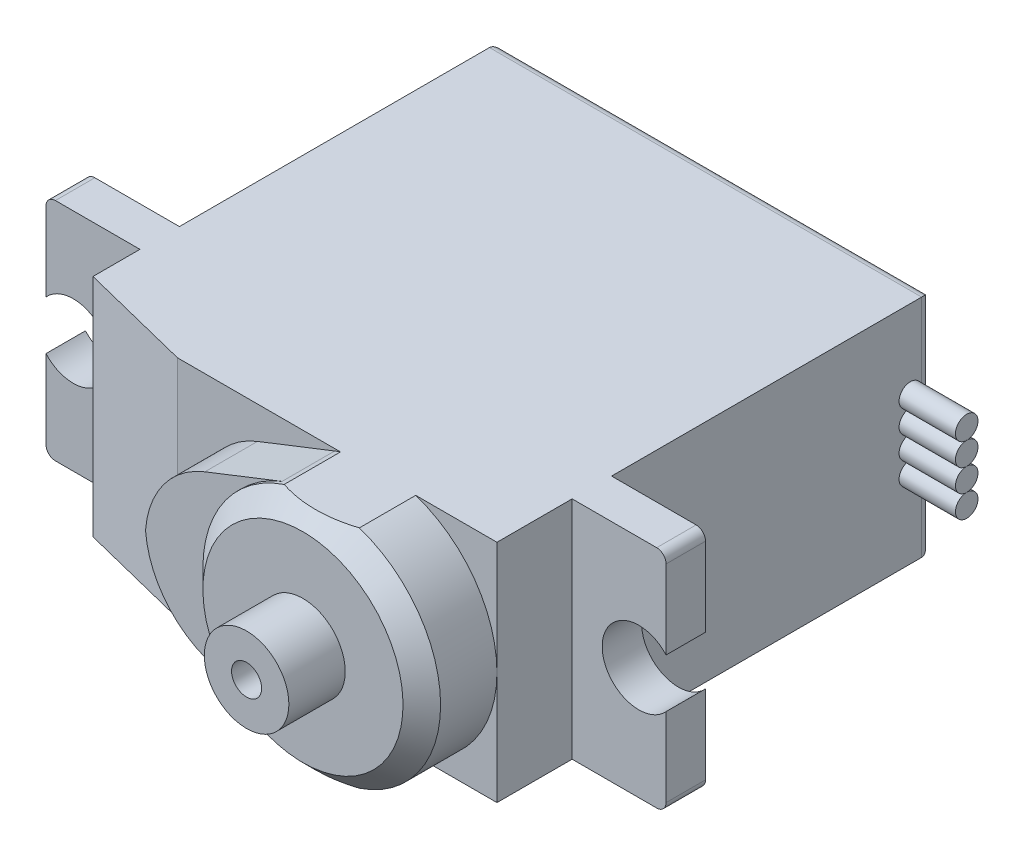
SolidWorks part; units mm, degrees
ref_plane "Plan de face" through (0, 0, 0) normal (0, 0, 1) x (1, 0, 0)
ref_plane "Plan de dessus" through (0, 0, 0) normal (0, 1, 0) x (1, 0, 0)
ref_plane "Plan de droite" through (0, 0, 0) normal (1, 0, 0) x (0, 0, -1)
sketch "Esquisse1" plane through (0, 0, 0) normal (0, 0, 1) x (1, 0, 0)
  line L1 (-11.5, -6) -> (11.5, -6)
  line L2 (-11.5, -6) -> (-11.5, 6)
  line L3 (-11.5, 6) -> (11.5, 6)
  line L4 (11.5, -6) -> (11.5, 6)
  line L5 (-11.5, -6) -> (11.5, 6) construction
  line L6 (-11.5, 6) -> (11.5, -6) construction
  point P0 (0, 0)
  dimension "D1" = 12
  dimension "D2" = 23
extrude "Boss.-Extru.1" add sketch "Esquisse1" along normal blind 17
sketch "Esquisse2" plane through (0, 0, 17) normal (0, 0, 1) x (1, 0, 0)
  line L0 (-18.1692, 0) -> (18.4767, 0) construction
  line L1 (-16, 6) -> (16, 6)
  line L2 (-16.5, 5.5) -> (-16.5, 1.3038)
  line L3 (-16, -6) -> (16, -6)
  line L4 (16.5, 5.5) -> (16.5, 1.3038)
  line L5 (-16.5, 6) -> (16.5, -6) construction
  line L6 (-16.5, -6) -> (16.5, 6) construction
  line L7 (16.5, 9.0964) -> (16.5, 1.3038) construction
  line L8 (13.1, 9.0964) -> (13.1, -8.505) construction
  line L9 (15.05, 9.0964) -> (15.05, -8.505) construction
  line L10 (16.5, -1.3038) -> (16.5, -5.5)
  line L11 (16.5, -1.3038) -> (16.5, -8.505) construction
  line L12 (16.5, 9.0964) -> (16.5, -8.505) construction
  line L13 (-16.5, 8.7179) -> (-16.5, 1.3038) construction
  line L14 (-13.1, 8.7179) -> (-13.1, -7.7006) construction
  line L15 (-15.05, 8.7179) -> (-15.05, -7.7006) construction
  line L16 (-16.5, -1.3038) -> (-16.5, -5.5)
  line L17 (-16.5, -1.3038) -> (-16.5, -7.7006) construction
  line L18 (-16.5, 8.7179) -> (-16.5, -7.7006) construction
  arc A0 (16.5, 1.3038) -> (16.5, -1.3038) centre (15.05, 0) ccw
  arc A1 (16, -6) -> (16.5, -5.5) centre (16, -5.5) ccw
  arc A2 (16, 6) -> (16.5, 5.5) centre (16, 5.5) cw
  arc A3 (-16.5, -1.3038) -> (-16.5, 1.3038) centre (-15.05, 0) ccw
  arc A4 (-16.5, -5.5) -> (-16, -6) centre (-16, -5.5) ccw
  arc A5 (-16, 6) -> (-16.5, 5.5) centre (-16, 5.5) ccw
  point P0 (0, 0)
  dimension "D5" = 0.5
  dimension "D8" = 0.5
  dimension "D1" = 12
  dimension "D2" = 33
  dimension "D3" = 3.4
  dimension "D4" = 1.95
  dimension "D6" = 3.4
  dimension "D7" = 1.95
extrude "Boss.-Extru.2" add sketch "Esquisse2" along normal blind 2.1
sketch "Esquisse3" plane through (0, 0, 19.1) normal (0, 0, 1) x (1, 0, 0)
  line L1 (-11.5, -6) -> (11.5, -6)
  line L2 (-11.5, -6) -> (-11.5, 6)
  line L3 (-11.5, 6) -> (11.5, 6)
  line L4 (11.5, -6) -> (11.5, 6)
  line L5 (-11.5, -6) -> (11.5, 6) construction
  line L6 (-11.5, 6) -> (11.5, -6) construction
  point P0 (0, 0)
  dimension "D1" = 12
  dimension "D2" = 23
extrude "Boss.-Extru.3" add sketch "Esquisse3" along normal blind 4
fillet "Congé1" radius 0.5 4 edges at (0, 6, 0) (-11.5, 0, 0) (0, -6, 0) (11.5, 0, 0)
sketch "Esquisse5" plane through (0, 0, 23.1) normal (0, 0, 1) x (1, 0, 0)
  line L0 (11.5, 8.2314) -> (11.5, -9.1478) construction
  line L1 (-1.15, 8.2314) -> (-1.15, -9.1478) construction
  line L2 (-1.15, 0) -> (11.5, 0) construction
  line L3 (3.1736, 6) -> (7.1764, 6)
  line L5 (3.1736, -6) -> (7.1764, -6)
  arc A0 (3.1736, 6) -> (3.1736, -6) centre (5.175, 0) ccw
  arc A1 (7.1764, -6) -> (7.1764, 6) centre (5.175, 0) ccw
  dimension "D1" = 12.65
extrude "Boss.-Extru.4" add sketch "Esquisse5" along normal blind 4
chamfer "Chanfrein1" distance 1 angle 45 1 edges at (11.5, 0, 27.1)
sketch "Esquisse6" plane through (0, -6, 0) normal (0, -1, 0) x (1, 0, 0)
  line L0 (-15.7281, 23.1) -> (17.6761, 23.1) construction
  line L1 (-11.5, 24.4623) -> (-11.5, -1.655) construction
  line L2 (-5.5, 24.4623) -> (-5.5, -1.655) construction
  line L3 (-15.7281, 21.6) -> (17.6761, 21.6) construction
  line L4 (-11.5, 21.6) -> (-5.5, 23.1)
  line L5 (-5.5, 23.1) -> (-11.5, 23.1)
  line L6 (-11.5, 23.1) -> (-11.5, 21.6)
  dimension "D1" = 6
  dimension "D2" = 1.5
extrude "Enlèv. mat.-Extru.1" cut sketch "Esquisse6" against normal through all
sketch "Esquisse7" plane through (0, 0, 23.1) normal (0, 0, 1) x (1, 0, 0)
  line L0 (11.4823, 7.3939) -> (11.4823, -9.7477) construction
  line L1 (-4.4177, 7.3939) -> (-4.4177, 0) construction
  line L2 (-1.2445, -4.2751) -> (2.8641, -5.8877)
  line L3 (-16.1024, 0) -> (25.4478, 0) construction
  line L4 (-1.2445, 4.2751) -> (2.8641, 5.8877)
  line L5 (-4.4177, 7.3939) -> (-4.4177, -9.7477) construction
  arc A0 (-1.2445, 4.2751) -> (-4.4033, 0) centre (0.5823, -0.3792) ccw
  arc A1 (3.1736, 6) -> (3.1736, -6) centre (5.175, 0) ccw construction
  arc A2 (2.8641, 5.8877) -> (2.8641, -5.8877) centre (5.175, 0) ccw
  arc A3 (-1.2445, -4.2751) -> (-4.4033, 0) centre (0.5823, 0.3792) cw
  dimension "D1" = 15.9
extrude "Boss.-Extru.5" add sketch "Esquisse7" along normal blind 2.8
sketch "Esquisse8" plane through (0, 0, 27.1) normal (0, 0, 1) x (1, 0, 0)
  circle A0 centre (5.175, 0) radius 2.25
  circle A1 centre (5.175, 0) radius 0.8
  dimension "D1" = 4.5
  dimension "D2" = 1.6
extrude "Boss.-Extru.6" add sketch "Esquisse8" along normal blind 3 separate body
sketch "Esquisse9" plane through (11.5, 0, 0) normal (1, 0, 0) x (0, 0, -1)
  line L0 (-0.5, 6) -> (-0.5, -6) construction
  line L1 (-1.7, 6) -> (-1.7, -6) construction
  line L2 (-0.5, 6) -> (-1.7, 6) construction
  line L3 (-0.5, 1.2) -> (-1.7, 0) construction
  line L4 (-0.5, -6) -> (-1.7, -6) construction
  line L5 (-1.7, 0) -> (-0.5, -1.2) construction
  line L6 (-1.7, 7.0126) -> (-1.7, -8.7464) construction
  line L7 (-0.5, 7.0126) -> (-0.5, -8.7464) construction
  line L8 (-1.7, 0) -> (-0.5, 0) construction
  line L9 (-1.7, -1.2) -> (-0.5, -1.2) construction
  line L10 (-1.7, 1.2) -> (-0.5, 1.2) construction
  line L11 (-1.7, 2.4) -> (-0.5, 2.4) construction
  line L12 (-1.7, -2.4) -> (-0.5, -2.4) construction
  line L13 (-1.7, 2.4) -> (-0.5, 1.2) construction
  line L14 (-0.5, -1.2) -> (-1.7, -2.4) construction
  line L15 (-0.5, -2.4) -> (-1.7, -1.2) construction
  line L16 (-1.7, -1.2) -> (-0.5, 0) construction
  line L17 (-0.5, 0) -> (-1.7, 1.2) construction
  line L18 (-1.7, 1.2) -> (-0.5, 2.4) construction
  circle A0 centre (-1.1, 1.8) radius 0.6
  circle A1 centre (-1.1, 0.6) radius 0.6
  circle A2 centre (-1.1, -0.6) radius 0.6
  circle A3 centre (-1.1, -1.8) radius 0.6
  dimension "D1" = 1.2
  dimension "D2" = 1.2
  dimension "D3" = 1.2
  dimension "D4" = 1.2
  dimension "D5" = 1.2
extrude "Boss.-Extru.7" add sketch "Esquisse9" along normal blind 3 separate body contours A0 | A1 | A2 | A3 region at (11.5, 1.8, 1.1) region at (11.5, -1.8, 1.1) region at (11.5, -0.6, 1.1) region at (11.5, 0.6, 1.1)
